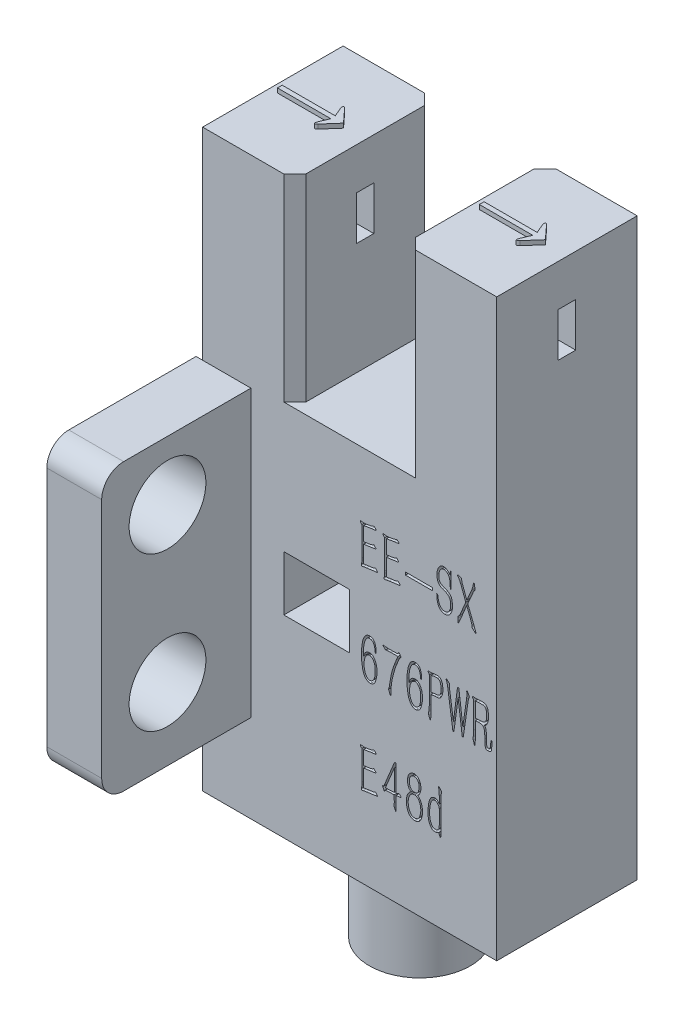
SolidWorks part; units mm, degrees
ref_plane "前视基准面" through (0, 0, 0) normal (0, 0, 1) x (1, 0, 0)
ref_plane "上视基准面" through (0, 0, 0) normal (0, 1, 0) x (1, 0, 0)
ref_plane "右视基准面" through (0, 0, 0) normal (1, 0, 0) x (0, 0, -1)
ref_plane "基准面1" through (-7, 0, 0) normal (1, 0, 0) x (0, 0, -1)
sketch "草图2" plane through (0, 0, 0) normal (0, 0, 1) x (1, 0, 0)
  line L0 (0, -13.1) -> (0, 13.1) construction
  line L1 (-6.7, -13.1) -> (6.7, -13.1)
  line L2 (-6.7, -13.1) -> (-6.7, 13.1)
  line L3 (-6.7, 13.1) -> (-2.5, 13.1)
  line L4 (6.7, -13.1) -> (6.7, 13.1)
  line L5 (-6.7, -13.1) -> (6.7, 13.1) construction
  line L6 (-6.7, 13.1) -> (6.7, -13.1) construction
  line L7 (-6.7, 9.746) -> (6.7, 9.746) construction
  line L8 (2.5, 4.1) -> (-2.5, 4.1)
  line L9 (2.5, 4.1) -> (2.5, 13.1)
  line L11 (-2.5, 4.1) -> (-2.5, 13.1)
  line L12 (2.5, 4.1) -> (-2.5, 13.1) construction
  line L13 (2.5, 13.1) -> (-2.5, 4.1) construction
  line L14 (0, -4.3) -> (-3, -4.3)
  line L15 (0, -4.3) -> (0, -1.8)
  line L16 (0, -1.8) -> (-3, -1.8)
  line L17 (-3, -4.3) -> (-3, -1.8)
  line L18 (2.5, 13.1) -> (6.7, 13.1)
  point P0 (0, 0)
  point P5 (0, 8.6)
  point P9 (0, 0)
  dimension "D1" = 26.2
  dimension "D2" = 13.4
  dimension "D3" = 5
  dimension "D4" = 3
  dimension "D5" = 2.5
  dimension "D6" = 8.4
  dimension "D7" = 9
  dimension "D8" = 3.354
extrude "凸台-拉伸1" add sketch "草图2" along normal mid plane 6.4 contours L9 L18 L4 L1 L2 L3 L11 L8 | L15 L14 L17 L16
sketch "草图4" plane through (-7, 0, 0) normal (-1, 0, 0) x (0, 0, 1)
  line L0 (3.2, -13.1) -> (3.2, 13.1) construction
  line L1 (3.2, -9.1) -> (9, -9.1)
  line L2 (3.2, -9.1) -> (3.2, 3.9)
  line L3 (3.2, 3.9) -> (9, 3.9)
  line L4 (10, -8.1) -> (10, 2.9)
  line L5 (-3.2, -13.1) -> (-3.2, 13.1) construction
  line L6 (3.2, 13.1) -> (-3.2, 13.1) construction
  line L7 (3.2, -13.1) -> (-3.2, -13.1) construction
  line L9 (-0.4, 9.2) -> (0.4, 9.2)
  line L10 (-0.4, 9.2) -> (-0.4, 11.2)
  line L11 (-0.4, 11.2) -> (0.4, 11.2)
  line L12 (0.4, 9.2) -> (0.4, 11.2)
  line L13 (-0.4, 9.2) -> (0.4, 11.2) construction
  line L14 (-0.4, 11.2) -> (0.4, 9.2) construction
  circle A0 centre (7, 1.2) radius 1.75
  circle A1 centre (7, -5.8) radius 1.75
  arc A2 (9, -9.1) -> (10, -8.1) centre (9, -8.1) ccw
  arc A3 (9, 3.9) -> (10, 2.9) centre (9, 2.9) cw
  point P8 (0, 13.1)
  point P18 (0, 10.2)
  point P25 (10, -9.1)
  point P28 (10, 3.9)
  dimension "D3" = 3.5
  dimension "D4" = 7
  dimension "D7" = 3.3
  dimension "D11" = 1
  dimension "D1" = 13.2
  dimension "D2" = 13
  dimension "D5" = 7
  dimension "D6" = 4
  dimension "D8" = 0.8
  dimension "D9" = 2
  dimension "D10" = 9
extrude "凸台-拉伸2" add sketch "草图4" against normal blind 2.5 contours A0 | A1 | L2 L3 A3 L4 A2 L1 | A0 | A1 region at (-7, 1.2, 7) region at (-7, -5.8, 7)
extrude "切除-拉伸2" cut sketch "草图4<6>" against normal through all contours L10 L11 L12 L9
sketch "草图4<6>" plane through (-7, 0, 0) normal (-1, 0, 0) x (0, 0, 1) same geometry as "草图4"
sketch "草图5" plane through (0, 13.1, 0) normal (0, 1, 0) x (1, 0, 0)
  line L0 (-6.7, -3.2) -> (-6.7, 3.2) construction
  text T0 "→\r\n"
  text T1 "→\r\n"
extrude "凸台-拉伸3" add sketch "草图5" along normal blind 0.2
chamfer "倒角1" distance 0.5 angle 45 4 edges at (2.5, 8.6, 3.2) (2.5, 8.6, -3.2) (-2.5, 8.6, -3.2) (-2.5, 8.6, 3.2)
sketch "草图6" plane through (0, -13.1, 0) normal (0, -1, 0) x (1, 0, 0)
  circle A0 centre (0, 0) radius 2.3
  dimension "D1" = 4.6
extrude "凸台-拉伸4" add sketch "草图6" along normal blind 4 contours A0
sketch "草图7" plane through (0, 0, 3.2) normal (0, 0, 1) x (1, 0, 0)
  text T0 "EE-SX\r\n676PWR\r\nE48d" font "汉仪长仿宋体" height 2
extrude "切除-拉伸3" cut sketch "草图7" against normal blind 1
